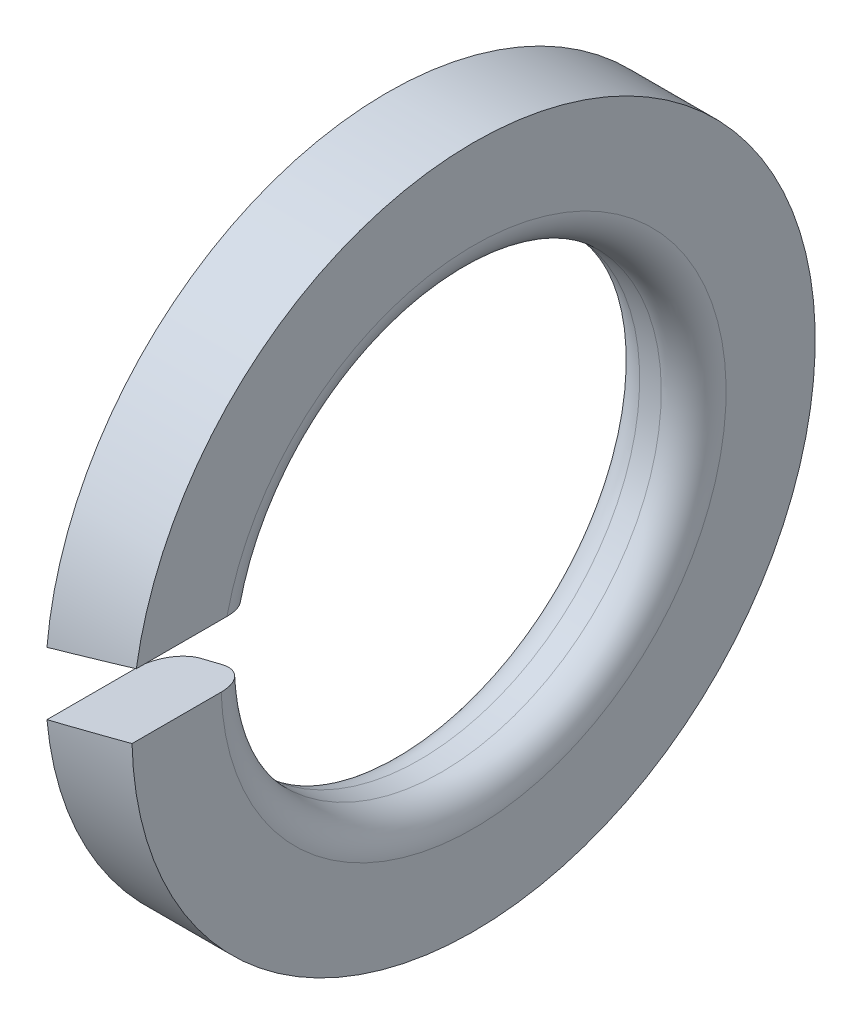
SolidWorks part; units mm, degrees
note: '?' marks a value the reader was unsure of.
ref_plane "Płaszczyzna przednia" through (0, 0, 0) normal (0, 0, 1) x (1, 0, 0)
ref_plane "Płaszczyzna górna" through (0, 0, 0) normal (0, 1, 0) x (1, 0, 0)
ref_plane "Płaszczyzna prawa" through (0, 0, 0) normal (1, 0, 0) x (0, 0, -1)
sketch "Szkic1" plane through (0, 0, 0) normal (0, 1, 0) x (1, 0, 0)
  line L0 (0, 8.15) -> (3.2, 8.15)
  line L1 (3.2, 8.15) -> (3.2, 12.65)
  line L2 (3.2, 12.65) -> (0, 12.65)
  line L3 (0, 12.65) -> (0, 8.15)
  line L4 (1, 0) -> (-1, 0) construction
revolve "Obrót1" add sketch "Szkic1" angle 180 about L4
sketch "Szkic2" plane through (0, 0, 0) normal (0, 0, 1) x (1, 0, 0)
  line L0 (-3.2, 0.3021) -> (-3.2, -2.0169)
  line L1 (-3.2, -2.0169) -> (4.85, 0.14)
  line L2 (4.85, 0.14) -> (4.85, 2.4591)
  line L3 (4.85, 2.4591) -> (-3.2, 0.3021)
extrude "Wytnij-wyciągnięcie1" cut sketch "Szkic2" along normal blind 32.6
sketch "Szkic3" plane through (0, 0, 0) normal (0, 0, 1) x (1, 0, 0)
  line L0 (0, 5.4333) -> (3.2, 5.4333)
  line L1 (3.2, 5.4333) -> (3.2, 9.35)
  line L2 (2, 8.15) -> (1.2, 8.15)
  line L3 (0, 9.35) -> (0, 5.4333)
  line L4 (1, 0) -> (-1, 0) construction
  arc A0 (3.2, 9.35) -> (2, 8.15) centre (2, 9.35) cw
  arc A1 (1.2, 8.15) -> (0, 9.35) centre (1.2, 9.35) cw
revolve "Wycięcie-obrót1" cut sketch "Szkic3" angle 360 about L4
ref_plane "Płaszczyzna1" through (3.2, 0, 0) normal (1, 0, 0) x (0, 0, -1)
ref_plane "IP1 XY" through (0, 0, 0) normal (1, 0, 0) x (0, 0, -1)
ref_plane "IP1 XZ" through (0, 0, 0) normal (0, -1, 0) x (-1, 0, 0)
ref_plane "IP1 YZ" through (0, 0, 0) normal (0, 0, -1) x (-1, 0, 0)
ref_axis "IP1 X" through (0, 0, 80.9) along (0, 0, -1)?
ref_axis "IP1 Y" through (0, -50, 0) along (0, 1, 0)?
ref_axis "IP1 Z" through (80.9, 0, 0) along (-1, 0, 0)?
sketch3d "IP1"
  point P0 (0, 0, 0)
ref_plane "IP2 XY" through (3.2, 0, 0) normal (1, 0, 0) x (0, 0, -1)
ref_plane "IP2 XZ" through (0, 0, 0) normal (0, -1, 0) x (-1, 0, 0)
ref_plane "IP2 YZ" through (0, 0, 0) normal (0, 0, -1) x (-1, 0, 0)
ref_axis "IP2 X" through (3.2, 0, 80.9) along (0, 0, -1)?
ref_axis "IP2 Y" through (3.2, -50, 0) along (0, 1, 0)?
ref_axis "IP2 Z" through (80.9, 0, 0) along (-1, 0, 0)?
sketch3d "IP2"
  point P0 (3.2, 0, 0)
